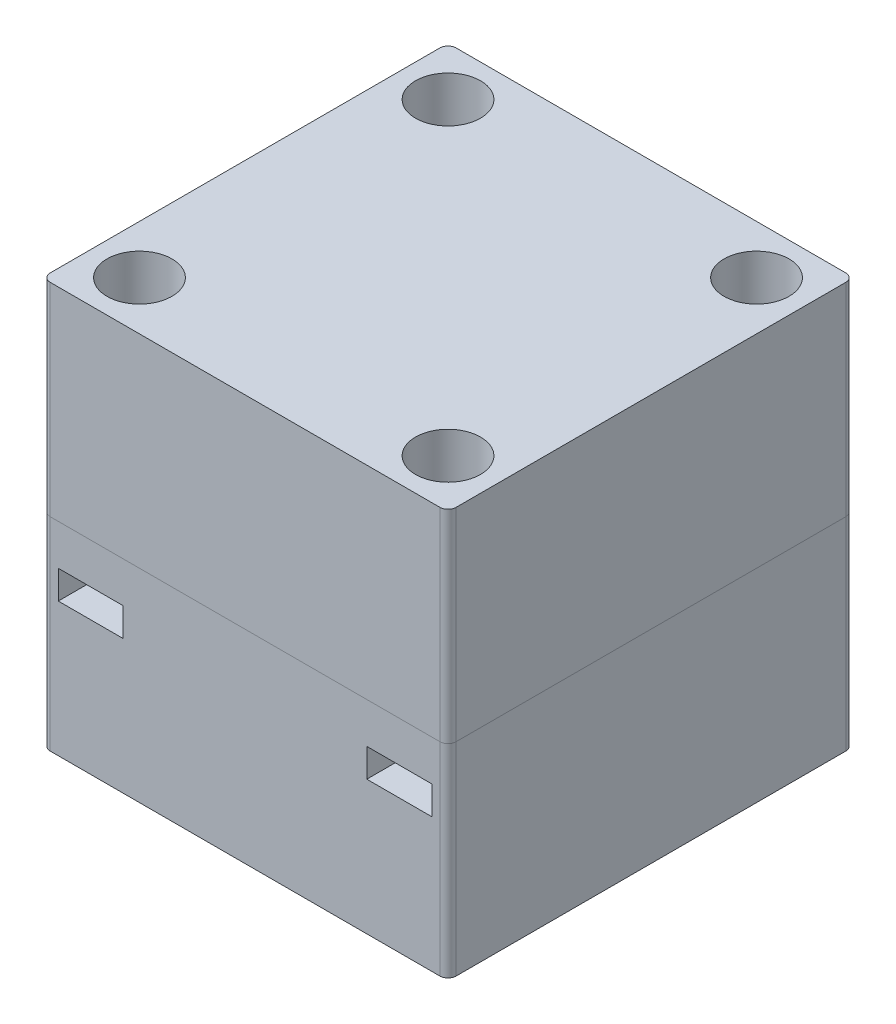
SolidWorks part; units mm, degrees
note: The reader was unsure of these and kept them because the rebuilt part matched: shared geometry of "Sketch3<3>", "Sketch3<4>", "Sketch2<2>", "Sketch3<5>", "Sketch3<6>".
ref_plane "Front Plane" through (0, 0, 0) normal (0, 0, 1) x (1, 0, 0)
ref_plane "Top Plane" through (0, 0, 0) normal (0, 1, 0) x (1, 0, 0)
ref_plane "Right Plane" through (0, 0, 0) normal (1, 0, 0) x (0, 0, -1)
sketch "Sketch1" plane through (0, 0, 0) normal (0, 1, 0) x (1, 0, 0)
  line L1 (-25, 25) -> (25, 25)
  line L2 (-25, 25) -> (-25, -25)
  line L3 (-25, -25) -> (25, -25)
  line L4 (25, 25) -> (25, -25)
  line L5 (-25, 25) -> (25, -25) construction
  line L6 (-25, -25) -> (25, 25) construction
  point P0 (0, 0)
  dimension "D1" = 50
  dimension "D2" = 50
extrude "Boss-Extrude1" add sketch "Sketch1" along normal mid plane 50
split "Split1" trim tools "Top Plane" bodies to split 101 resulting bodies 102 103
shell "Shell1" thickness 6 removed face at (0, 0, 0)
sketch "Sketch2" plane through (0, 0, 0) normal (0, 1, 0) x (1, 0, 0)
  line L0 (19, 19) -> (-19, 19) construction
  line L1 (-19, 19) -> (-19, -19) construction
  line L2 (0, 26.8836) -> (0, -28.1688) construction
  line L3 (-33.2385, 0) -> (38.808, 0) construction
  line L4 (-19, 9) -> (-19, 19)
  line L5 (-19, 19) -> (-9, 19)
  line L6 (19, 19) -> (9, 19)
  line L7 (19, 9) -> (19, 19)
  line L8 (19, -9) -> (19, -19)
  line L9 (19, -19) -> (9, -19)
  line L10 (-19, -19) -> (-9, -19)
  line L11 (-19, -9) -> (-19, -19)
  arc A0 (-9, 19) -> (-19, 9) centre (-19, 19) cw
  arc A1 (9, 19) -> (19, 9) centre (19, 19) ccw
  arc A2 (9, -19) -> (19, -9) centre (19, -19) cw
  arc A3 (-9, -19) -> (-19, -9) centre (-19, -19) ccw
  dimension "D1" = 10
extrude "Boss-Extrude2" add sketch "Sketch2" against normal up to next
fillet "Fillet2" radius 2 8 edges at (19, -9.5, -9) (9, -9.5, -19) (-9, -9.5, -19) (-19, -9.5, 9) (-9, -9.5, 19) (9, -9.5, 19) (19, -9.5, 9) (-19, -9.5, -9)
sketch "Sketch3" plane through (0, 0, 0) normal (0, 1, 0) x (1, 0, 0)
  line L40 (7.1678, 23.5) -> (-7.1678, 23.5)
  line L41 (23.5, -7.1678) -> (23.5, 7.1678)
  line L42 (-7.1678, -23.5) -> (7.1678, -23.5)
  line L43 (-23.5, 7.1678) -> (-23.5, -7.1678)
  line L44 (20.5, -7.1678) -> (20.5, 7.1678)
  line L45 (-7.1678, -20.5) -> (7.1678, -20.5)
  line L46 (-20.5, 7.1678) -> (-20.5, -7.1678)
  line L47 (7.1678, 20.5) -> (-7.1678, 20.5)
  line L48 (20.5, -7.1678) -> (20.5, 7.1678)
  line L49 (-7.1678, -20.5) -> (7.1678, -20.5)
  line L50 (-20.5, 7.1678) -> (-20.5, -7.1678)
  line L51 (7.1678, 20.5) -> (-7.1678, 20.5)
  line L52 (-23, 19) -> (-23, 25)
  line L53 (25, 25) -> (-25, 25) construction
  line L54 (-23, 25) -> (-15, 25)
  line L55 (-15, 25) -> (-15, 19)
  line L56 (0, 31.9371) -> (0, -29.8571) construction
  line L57 (-39.132, 0) -> (41.2005, 0) construction
  line L58 (15, 25) -> (15, 19)
  line L59 (23, 25) -> (15, 25)
  line L60 (23, 19) -> (23, 25)
  line L61 (23, -19) -> (23, -25)
  line L62 (23, -25) -> (15, -25)
  line L63 (15, -25) -> (15, -19)
  line L64 (-15, -25) -> (-15, -19)
  line L65 (-23, -25) -> (-15, -25)
  line L66 (-23, -19) -> (-23, -25)
  arc A103 (-18.0833, 13.5769) -> (-13.5769, 18.0833) centre (-19, 19) ccw
  arc A104 (-7.1678, 23.5) -> (-13.5769, 18.0833) centre (-7.1678, 17) ccw
  arc A105 (13.5769, 18.0833) -> (7.1678, 23.5) centre (7.1678, 17) ccw
  arc A106 (13.5769, 18.0833) -> (18.0833, 13.5769) centre (19, 19) ccw
  arc A107 (23.5, 7.1678) -> (18.0833, 13.5769) centre (17, 7.1678) ccw
  arc A108 (18.0833, -13.5769) -> (23.5, -7.1678) centre (17, -7.1678) ccw
  arc A109 (18.0833, -13.5769) -> (13.5769, -18.0833) centre (19, -19) ccw
  arc A110 (7.1678, -23.5) -> (13.5769, -18.0833) centre (7.1678, -17) ccw
  arc A111 (-13.5769, -18.0833) -> (-7.1678, -23.5) centre (-7.1678, -17) ccw
  arc A112 (-13.5769, -18.0833) -> (-18.0833, -13.5769) centre (-19, -19) ccw
  arc A113 (-23.5, -7.1678) -> (-18.0833, -13.5769) centre (-17, -7.1678) ccw
  arc A114 (-18.0833, 13.5769) -> (-23.5, 7.1678) centre (-17, 7.1678) ccw
  arc A115 (20.5, 7.1678) -> (17.5833, 10.6189) centre (17, 7.1678) ccw
  arc A116 (10.6189, 17.5833) -> (17.5833, 10.6189) centre (19, 19) ccw
  arc A117 (10.6189, 17.5833) -> (7.1678, 20.5) centre (7.1678, 17) ccw
  arc A118 (17.5833, -10.6189) -> (20.5, -7.1678) centre (17, -7.1678) ccw
  arc A119 (17.5833, -10.6189) -> (10.6189, -17.5833) centre (19, -19) ccw
  arc A120 (7.1678, -20.5) -> (10.6189, -17.5833) centre (7.1678, -17) ccw
  arc A121 (-10.6189, -17.5833) -> (-7.1678, -20.5) centre (-7.1678, -17) ccw
  arc A122 (-10.6189, -17.5833) -> (-17.5833, -10.6189) centre (-19, -19) ccw
  arc A123 (-20.5, -7.1678) -> (-17.5833, -10.6189) centre (-17, -7.1678) ccw
  arc A124 (-17.5833, 10.6189) -> (-20.5, 7.1678) centre (-17, 7.1678) ccw
  arc A125 (-7.1678, 20.5) -> (-10.6189, 17.5833) centre (-7.1678, 17) ccw
  arc A126 (-17.5833, 10.6189) -> (-10.6189, 17.5833) centre (-19, 19) ccw
  arc A127 (20.5, 7.1678) -> (17.5833, 10.6189) centre (17, 7.1678) ccw
  arc A128 (10.6189, 17.5833) -> (17.5833, 10.6189) centre (19, 19) ccw
  arc A129 (10.6189, 17.5833) -> (7.1678, 20.5) centre (7.1678, 17) ccw
  arc A130 (17.5833, -10.6189) -> (20.5, -7.1678) centre (17, -7.1678) ccw
  arc A131 (17.5833, -10.6189) -> (10.6189, -17.5833) centre (19, -19) ccw
  arc A132 (7.1678, -20.5) -> (10.6189, -17.5833) centre (7.1678, -17) ccw
  arc A133 (-10.6189, -17.5833) -> (-7.1678, -20.5) centre (-7.1678, -17) ccw
  arc A134 (-10.6189, -17.5833) -> (-17.5833, -10.6189) centre (-19, -19) ccw
  arc A135 (-20.5, -7.1678) -> (-17.5833, -10.6189) centre (-17, -7.1678) ccw
  arc A136 (-17.5833, 10.6189) -> (-20.5, 7.1678) centre (-17, 7.1678) ccw
  arc A137 (-7.1678, 20.5) -> (-10.6189, 17.5833) centre (-7.1678, 17) ccw
  arc A138 (-17.5833, 10.6189) -> (-10.6189, 17.5833) centre (-19, 19) ccw
  circle A139 centre (-19, 19) radius 2
  circle A140 centre (19, 19) radius 2
  circle A141 centre (19, -19) radius 2
  circle A142 centre (-19, -19) radius 2
  arc A143 (-23, 19) -> (-15, 19) centre (-19, 19) ccw
  arc A144 (23, 19) -> (15, 19) centre (19, 19) cw
  circle A145 centre (19, 19) radius 2
  circle A146 centre (19, -19) radius 2
  arc A147 (23, -19) -> (15, -19) centre (19, -19) ccw
  circle A148 centre (19, -19) radius 2
  arc A149 (-23, -19) -> (-15, -19) centre (-19, -19) cw
  circle A150 centre (-19, -19) radius 2
  dimension "D3" = 4
  dimension "D4" = 8
  dimension "D1" = 1.5
  dimension "D2" = 3
extrude "Cut-Extrude1" cut sketch "Sketch3" against normal blind 5 contours A103 A114 L43 A113 A112 A111 L42 A110 A109 A108 L41 A107 A106 A105 L40 A104 A136 A138 A137 L51 A129 A128 A127 L48 A130 A131 A132 L49 A133 A134 A135 L50
extrude "Cut-Extrude2" cut sketch "Sketch3<3>" against normal through all contours A142 | A140 | A141 | A139
sketch "Sketch3<3>" plane through (0, 0, 0) normal (0, 1, 0) x (1, 0, 0) same geometry as "Sketch3"
extrude "Cut-Extrude3" cut sketch "Sketch3<4>" against normal blind 3.5 from offset 5 contours L52 L54 L55 A143 | L58 A144 L60 L59 | L64 A149 L66 L65 | L63 A147 L61 L62 offset against normal yes
sketch "Sketch3<4>" plane through (0, 0, 0) normal (0, 1, 0) x (1, 0, 0) same geometry as "Sketch3"
shell "Shell2" thickness 6 removed face at (0, 0, 0)
extrude "Boss-Extrude4" add sketch "Sketch2<2>" along normal up to next
sketch "Sketch2<2>" plane through (0, 0, 0) normal (0, 1, 0) x (1, 0, 0) same geometry as "Sketch2"
fillet "Fillet3" radius 2 8 edges at (-19, 9.5, -9) (-9, 9.5, -19) (9, 9.5, -19) (19, 9.5, -9) (19, 9.5, 9) (9, 9.5, 19) (-9, 9.5, 19) (-19, 9.5, 9)
extrude "Boss-Extrude3" add sketch "Sketch3<5>" against normal blind 3 contours A103 A114 L43 A113 A112 A111 L42 A110 A109 A108 L41 A107 A106 A105 L40 A104 A136 A138 A137 L51 A129 A128 A127 L48 A130 A131 A132 L49 A133 A134 A135 L50
sketch "Sketch3<5>" plane through (0, 0, 0) normal (0, 1, 0) x (1, 0, 0) same geometry as "Sketch3"
extrude "Cut-Extrude4" cut sketch "Sketch3<6>" along normal through all contours A142 | A141 | A139 | A140
sketch "Sketch3<6>" plane through (0, 0, 0) normal (0, 1, 0) x (1, 0, 0) same geometry as "Sketch3"
sketch "Sketch4" plane through (0, 0, 0) normal (0, -1, 0) x (-1, 0, 0)
  line L0 (0, -32.2346) -> (0, 34.9079) construction
  line L1 (41.18, 0) -> (-47.6578, 0) construction
  circle A0 centre (19, -19) radius 4
  circle A1 centre (-19, -19) radius 4
  circle A2 centre (-19, 19) radius 4
  circle A3 centre (19, 19) radius 4
  dimension "D1" = 8
extrude "Cut-Extrude5" cut sketch "Sketch4" against normal through all from offset 10 offset against normal yes
fillet "Fillet4" radius 1 4 edges at (25, -12.5, 25) (25, -12.5, -25) (-25, -12.5, -25) (-25, -12.5, 25)
fillet "Fillet5" radius 1 4 edges at (25, 12.5, 25) (-25, 12.5, 25) (25, 12.5, -25) (-25, 12.5, -25)
other "Save Bodies1"
